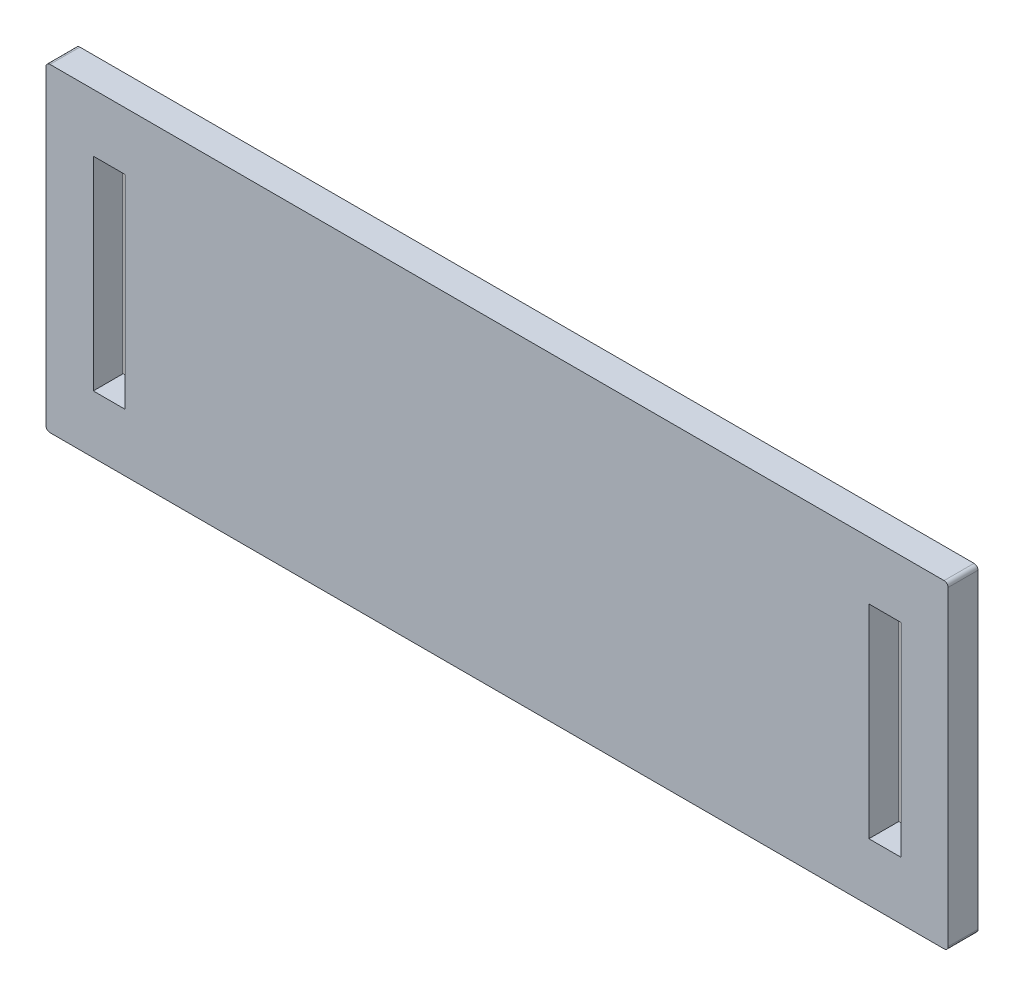
SolidWorks part; units mm, degrees
ref_plane "Front Plane" through (0, 0, 0) normal (0, 0, 1) x (1, 0, 0)
ref_plane "Top Plane" through (0, 0, 0) normal (0, 1, 0) x (1, 0, 0)
ref_plane "Right Plane" through (0, 0, 0) normal (1, 0, 0) x (0, 0, -1)
sketch "Sketch1" plane through (0, 0, 0) normal (0, 0, 1) x (1, 0, 0)
  line L0 (22.625, 0) -> (22.625, 4.9) construction
  line L1 (0.2, 0) -> (45.05, 0)
  line L2 (0, 0.2) -> (0, 15.8)
  line L3 (0.2, 16) -> (45.05, 16)
  line L4 (45.25, 0.2) -> (45.25, 15.8)
  line L5 (2.3721, 13.1) -> (3.9721, 13.1)
  line L6 (2.3721, 13.1) -> (2.3721, 2.9)
  line L7 (2.3721, 2.9) -> (3.9721, 2.9)
  line L8 (3.9721, 13.1) -> (3.9721, 2.9)
  line L9 (41.2779, 13.1) -> (41.2779, 2.9)
  line L10 (42.8779, 2.9) -> (41.2779, 2.9)
  line L11 (42.8779, 13.1) -> (42.8779, 2.9)
  line L12 (42.8779, 13.1) -> (41.2779, 13.1)
  arc A0 (45.05, 16) -> (45.25, 15.8) centre (45.05, 15.8) cw
  arc A1 (45.05, 0) -> (45.25, 0.2) centre (45.05, 0.2) ccw
  arc A2 (0.2, 0) -> (0, 0.2) centre (0.2, 0.2) cw
  arc A3 (0, 15.8) -> (0.2, 16) centre (0.2, 15.8) cw
  point P9 (2.3721, 8)
  point P10 (0, 8)
  point P19 (45.25, 16)
  point P22 (45.25, 0)
  point P25 (0, 0)
  point P28 (0, 16)
  dimension "D5" = 0.2
  dimension "D1" = 45.25
  dimension "D2" = 16
  dimension "D3" = 1.6
  dimension "D4" = 10.2
base flange "Base-Flange1" sketch "Sketch1" thickness 1.5 reverse thickness direction no parameters "D1"=2
sketch "Sketch2" plane through (0, 0, -1.5) normal (0, 0, -1) x (-1, 0, 0)
  line L0 (-45.05, 16) -> (-0.2, 16) construction
  line L1 (-35.25, 16) -> (-42.25, 16)
  line L2 (-35.25, 16) -> (-35.25, 19.5)
  line L4 (-42.25, 16) -> (-42.25, 19.5)
  line L5 (-45.25, 0.2) -> (-45.25, 15.8) construction
  arc A0 (-35.25, 19.5) -> (-42.25, 19.5) centre (-38.75, 19) ccw
  circle A1 centre (-38.75, 19) radius 1.25
  dimension "D2" = 3
  dimension "D3" = 2.5
  dimension "D1" = 7
  dimension "D4" = 3
base flange "Tab1" [suppressed] sketch "Sketch2" thickness 1.5 reverse thickness direction no parameters "D1"=2
sketch "Bend-Lines1" [suppressed] plane through (0, 0, 0) normal (0, 1, 0) x (1, 0, 0)
sketch "Bounding-Box1" [suppressed] plane through (0, 0, 0) normal (0, 1, 0) x (1, 0, 0)
sheet metal parameters "Sheet-Metal1" thickness 1.5 parameters "D1"=2
flat pattern "Flat-Pattern1" [suppressed]
sketch "Bend-Lines2" plane through (0, 0, 0) normal (0, 1, 0) x (1, 0, 0)
sketch3d "Bounding-Box2" [suppressed]
  line L0 (-36.2, -15.8, 0) -> (0.2, -15.8, 0) construction
  line L1 (-36.2, 0.2, 0) -> (0.2, 0.2, 0) construction
  line L2 (-36.2, -15.8, 0) -> (-36.2, 0.2, 0) construction
  line L3 (0.2, -15.8, 0) -> (0.2, 0.2, 0) construction
sheet metal parameters "Sheet-Metal2" thickness 1.5 parameters "D1"=2
flat pattern "Flat-Pattern2"
sketch "Bend-Lines3" plane through (0, 0, 0) normal (0, 1, 0) x (1, 0, 0)
sketch3d "Bounding-Box3" [suppressed]
  line L0 (-36.2, -15.8, 0) -> (0.2, -15.8, 0) construction
  line L1 (-36.2, 6.7352, 0) -> (0.2, 6.7352, 0) construction
  line L2 (-36.2, -15.8, 0) -> (-36.2, 6.7352, 0) construction
  line L3 (0.2, -15.8, 0) -> (0.2, 6.7352, 0) construction
